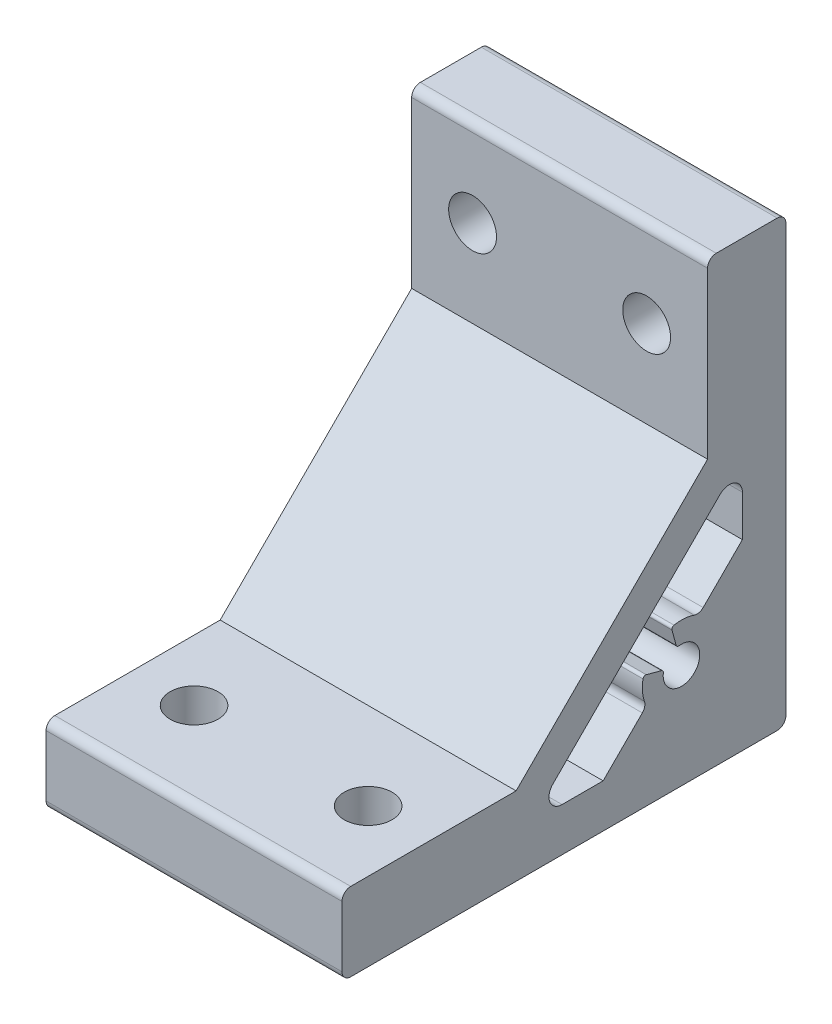
SolidWorks part; units mm, degrees
ref_plane "Front Plane" through (0, 0, 0) normal (0, 0, 1) x (1, 0, 0)
ref_plane "Top Plane" through (0, 0, 0) normal (0, 1, 0) x (1, 0, 0)
ref_plane "Right Plane" through (0, 0, 0) normal (1, 0, 0) x (0, 0, -1)
ref_plane "Plane1" through (0, 0, 0) normal (1, 0, 0) x (0, 0, -1)
sketch "Sketch1" plane through (0, 0, 0) normal (1, 0, 0) x (0, 0, -1)
  line L0 (-50, 0) -> (-1, 0)
  line L1 (0, 1) -> (0, 50)
  line L2 (-1, 51) -> (-8, 51)
  line L3 (-9, 50) -> (-9, 31)
  line L4 (-9, 31) -> (-31, 9)
  line L5 (-31, 9) -> (-50, 9)
  line L6 (-51, 8) -> (-51, 1)
  line L7 (-25.7218, 5) -> (-20.9993, 5)
  line L8 (-20.9993, 5) -> (-16.494, 9.5052)
  line L9 (-16.0465, 13.0843) -> (-14.3, 12.6163)
  line L10 (-12.6163, 14.3) -> (-13.0843, 16.0465)
  line L11 (-9.5052, 16.494) -> (-5, 20.9993)
  line L12 (-5, 20.9993) -> (-5, 25.7218)
  line L13 (-7.5607, 26.7825) -> (-26.7825, 7.5607)
  line L14 (-1, 0) -> (0, 0) construction
  line L15 (0, 0) -> (0, 1) construction
  line L16 (-1, 1) -> (-40.8569, 40.8569) construction
  arc A0 (-51, 1) -> (-50, 0) centre (-50, 1) ccw
  arc A1 (-1, 0) -> (0, 1) centre (-1, 1) ccw
  arc A2 (0, 50) -> (-1, 51) centre (-1, 50) ccw
  arc A3 (-8, 51) -> (-9, 50) centre (-8, 50) ccw
  arc A4 (-50, 9) -> (-51, 8) centre (-50, 8) ccw
  arc A5 (-26.7825, 7.5607) -> (-25.7218, 5) centre (-25.7218, 6.5) ccw
  arc A6 (-16.494, 9.5052) -> (-16.2556, 10.5372) centre (-17.2013, 10.2122) ccw
  arc A7 (-16.2556, 10.5372) -> (-16.4188, 12.8512) centre (-12, 12) cw
  arc A8 (-16.4188, 12.8512) -> (-16.0465, 13.0843) centre (-16.1242, 12.7945) cw
  arc A9 (-14.3, 12.6163) -> (-14.0805, 12.2857) centre (-14.3777, 12.3265) cw
  arc A10 (-14.0805, 12.2857) -> (-12.2857, 14.0805) centre (-12, 12) ccw
  arc A11 (-12.2857, 14.0805) -> (-12.6163, 14.3) centre (-12.3265, 14.3777) cw
  arc A12 (-13.0843, 16.0465) -> (-12.8512, 16.4188) centre (-12.7945, 16.1242) cw
  arc A13 (-12.8512, 16.4188) -> (-10.5377, 16.2558) centre (-12, 12) cw
  arc A14 (-10.5377, 16.2558) -> (-9.5052, 16.494) centre (-10.2122, 17.2013) ccw
  arc A15 (-5, 25.7218) -> (-7.5607, 26.7825) centre (-6.5, 25.7218) ccw
  dimension "D7" = 2.1
  dimension "D13" = 4.5
  dimension "D14" = 1
  dimension "D1" = 9
  dimension "D2" = 9
  dimension "D3" = 51
  dimension "D4" = 51
  dimension "D5" = 5
  dimension "D6" = 5
  dimension "D8" = 12
  dimension "D9" = 20
  dimension "D10" = 20
  dimension "D11" = 4
  dimension "D12" = 5.9
extrude "Boss-Extrude1" add sketch "Sketch1" against normal blind 17 and the other way blind 17
ref_plane "Plane2" through (0, 0, 0) normal (0, 1, 0) x (-1, 0, 0)
sketch "Sketch2" plane through (0, 0, 0) normal (0, 1, 0) x (-1, 0, 0)
  circle A0 centre (10, 41) radius 2.75
extrude "Cut-Extrude1" cut sketch "Sketch2" along normal blind 9
ref_plane "Plane3" through (0, 0, 0) normal (0, 1, 0) x (-1, 0, 0)
sketch "Sketch3" plane through (0, 0, 0) normal (0, 1, 0) x (-1, 0, 0)
  circle A0 centre (-10, 41) radius 2.75
extrude "Cut-Extrude2" cut sketch "Sketch3" along normal blind 9
ref_plane "Plane4" through (0, 0, 0) normal (0, 0, 1) x (1, 0, 0)
sketch "Sketch4" plane through (0, 0, 0) normal (0, 0, 1) x (1, 0, 0)
  circle A0 centre (-10, 41) radius 2.75
extrude "Cut-Extrude3" cut sketch "Sketch4" along normal blind 9
ref_plane "Plane5" through (0, 0, 0) normal (0, 0, 1) x (1, 0, 0)
sketch "Sketch5" plane through (0, 0, 0) normal (0, 0, 1) x (1, 0, 0)
  circle A0 centre (10, 41) radius 2.75
extrude "Cut-Extrude4" cut sketch "Sketch5" along normal blind 9
